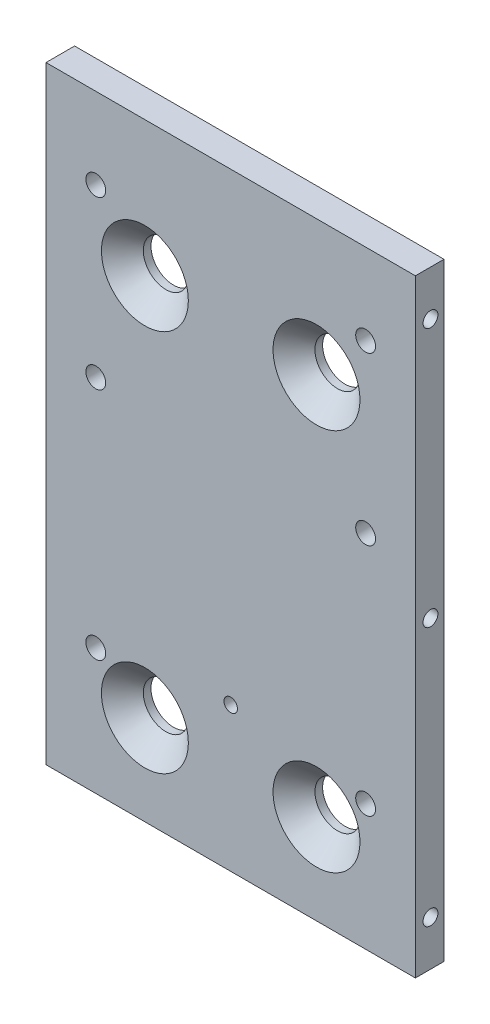
SolidWorks part; units mm, degrees
material "1060 Alloy"
ref_plane "Front Plane" through (0, 0, 0) normal (0, 0, 1) x (1, 0, 0)
ref_plane "Top Plane" through (0, 0, 0) normal (0, 1, 0) x (1, 0, 0)
ref_plane "Right Plane" through (0, 0, 0) normal (1, 0, 0) x (0, 0, -1)
sketch "Sketch1" plane through (0, 0, 0) normal (0, 0, 1) x (1, 0, 0)
  line L1 (41, 67.5) -> (-41, 67.5)
  line L2 (41, 67.5) -> (41, -67.5)
  line L3 (41, -67.5) -> (-41, -67.5)
  line L4 (-41, 67.5) -> (-41, -67.5)
  line L5 (41, 67.5) -> (-41, -67.5) construction
  line L6 (41, -67.5) -> (-41, 67.5) construction
  point P0 (0, 0)
  dimension "D1" = 82
  dimension "D2" = 135
extrude "Boss-Extrude1" add sketch "Sketch1" along normal blind 6.35
sketch "Sketch2" plane through (0, 0, 6.35) normal (0, 0, 1) x (1, 0, 0)
  line L0 (41, 67.5) -> (-41, 67.5) construction
  point P0 (-19.05, 37.5)
  point P1 (19.05, 37.5)
  point P2 (19.05, -47.5)
  point P3 (-19.05, -47.5)
  dimension "D1" = 38.1
  dimension "D2" = 19.05
  dimension "D3" = 85
  dimension "D4" = 30
hole_wizard "CSK for M8 Flat Head Machine Screw1" positions "Sketch3" profile "Sketch4" countersink size "M8" standard "ANSI Metric" end condition through all
sketch "Sketch3" plane through (0, 0, 6.35) normal (0, 0, 1) x (1, 0, 0)
  point P0 (-19.05, 37.5)
  point P3 (19.05, 37.5)
  point P6 (-19.05, -47.5)
  point P9 (19.05, -47.5)
sketch "Sketch4" plane through (-19.05, 37.5, 6.35) normal (1, 0, 0) x (0, -1, 0)
  line L0 (0, 0) -> (0, 6.35)
  line L1 (0, 6.35) -> (5, 6.35)
  line L2 (5, 6.35) -> (5, 4.65)
  line L3 (5, 4.65) -> (9.65, 0)
  line L5 (9.65, 0) -> (0, 0)
  line L6 (-5, 4.65) -> (-9.65, 0) construction
  line L11 (0, -6.35) -> (0, 107.95) construction
  dimension "Thru Hole Dia." = 10
  dimension "Thru Hole Depth" = 6.35
  dimension "Near C'Sink Dia." = 19.3
  dimension "Near C'Sink Angle" = 90
sketch "Sketch9" plane through (0, 0, 0) normal (0, 0, -1) x (-1, 0, 0)
  line L0 (41, -67.5) -> (-41, -67.5) construction
  circle A0 centre (0, -35.5) radius 1.5
  point P4 (0, -67.5)
  dimension "D1" = 3
  dimension "D2" = 32
extrude "Cut-Extrude2" cut sketch "Sketch9" against normal through all contours A0
sketch "Sketch11" plane through (0, 0, 0) normal (0, 0, -1) x (-1, 0, 0)
  point P0 (29.95, 49.5)
  point P1 (-29.95, 49.5)
  point P3 (29.95, 12.5)
  point P5 (-29.95, 12.5)
  point P7 (29.95, -39.5)
  point P9 (-29.95, -39.5)
hole_wizard "Hole1" positions "Sketch12" profile "Sketch13" legacy
sketch "Sketch12" plane through (0, 0, 0) normal (0, 0, -1) x (-1, 0, 0)
  point P0 (-29.95, -39.5)
  point P3 (-29.95, 12.5)
  point P6 (-29.95, 49.5)
  point P9 (29.95, 49.5)
  point P12 (29.95, 12.5)
  point P15 (29.95, -39.5)
sketch "Sketch13" plane through (29.95, -39.5, 0) normal (1, 0, 0) x (0, 1, 0)
  line L0 (0, 0) -> (0, 6.35)
  line L1 (0, 6.35) -> (2.2, 6.35)
  line L2 (2.2, 6.35) -> (2.2, 3)
  line L3 (2.2, 3) -> (3.75, 3)
  line L4 (3.75, 3) -> (3.75, 0)
  line L5 (3.75, 0) -> (0, 0)
  line L6 (0, 110) -> (0, -10) construction
  dimension "Diameter" = 4.4
  dimension "Depth" = 6.35
  dimension "C-Bore Diameter" = 7.5
  dimension "C-Bore Depth" = 3
sketch "Sketch14" plane through (41, 0, 0) normal (1, 0, 0) x (0, 0, -1)
  circle A0 centre (-3, 57.5) radius 1.65
  circle A1 centre (-3, 0) radius 1.65
  circle A2 centre (-3, -57.5) radius 1.65
  dimension "D1" = 3.3
extrude "Cut-Extrude4" cut sketch "Sketch14" against normal blind 15
mirror "Mirror1" about plane through (0, 0, 0) normal (1, 0, 0) of "Cut-Extrude4"
